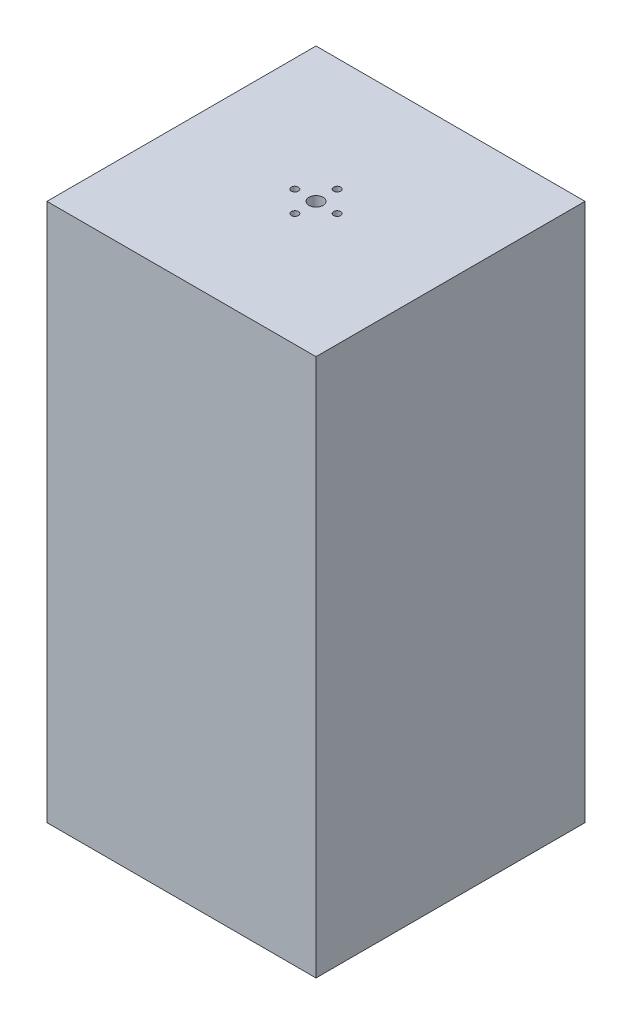
SolidWorks part; units mm, degrees
material "ABS_rapid_prototype"
ref_plane "Front Plane" through (0, 0, 0) normal (0, 0, 1) x (1, 0, 0)
ref_plane "Top Plane" through (0, 0, 0) normal (0, 1, 0) x (1, 0, 0)
ref_plane "Right Plane" through (0, 0, 0) normal (1, 0, 0) x (0, 0, -1)
sketch "Sketch1" plane through (0, 0, 0) normal (0, 0, 1) x (1, 0, 0)
  line L1 (0, 0) -> (76.2, 0)
  line L2 (0, 0) -> (0, 152.4)
  line L3 (0, 152.4) -> (76.2, 152.4)
  line L4 (76.2, 0) -> (76.2, 152.4)
  dimension "D1" = 152.4
  dimension "D2" = 76.2
extrude "Boss-Extrude1" add sketch "Sketch1" against normal blind 76.2
sketch "Sketch2" plane through (0, 0, 0) normal (0, -1, 0) x (1, 0, 0)
  line L0 (0, 0) -> (76.2, 0) construction
  line L1 (3.81, -3.81) -> (72.39, -3.81)
  line L2 (3.81, -3.81) -> (3.81, -72.39)
  line L3 (3.81, -72.39) -> (72.39, -72.39)
  line L4 (72.39, -3.81) -> (72.39, -72.39)
  line L5 (0, -76.2) -> (76.2, -76.2) construction
  line L6 (0, -76.2) -> (0, 0) construction
  line L7 (76.2, -76.2) -> (76.2, 0) construction
  dimension "D1" = 3.81
  dimension "D2" = 3.81
  dimension "D3" = 3.81
  dimension "D4" = 3.81
extrude "Cut-Extrude1" cut sketch "Sketch2" against normal blind 148.59
sketch "Sketch3" plane through (0, 152.4, 0) normal (0, 1, 0) x (1, 0, 0)
  line L0 (0, 76.2) -> (0, 0) construction
  line L1 (76.2, 0) -> (0, 0) construction
  circle A0 centre (38.1, 38.1) radius 2
  circle A1 centre (38.1, 44.1) radius 1
  circle A2 centre (38.1, 32.1) radius 1
  circle A3 centre (44.1, 38.1) radius 1
  circle A4 centre (32.1, 38.1) radius 1
  dimension "D1" = 4
  dimension "D4" = 2
  dimension "D5" = 6
  dimension "D2" = 38.1
  dimension "D3" = 38.1
  dimension "D6" = 38.1
  dimension "D7" = 6
  dimension "D8" = 38.1
  dimension "D9" = 6
  dimension "D10" = 38.1
  dimension "D11" = 6
  dimension "D12" = 38.1
extrude "Cut-Extrude2" cut sketch "Sketch3" against normal through all contours A2 | A1 | A0 | A3 | A4
